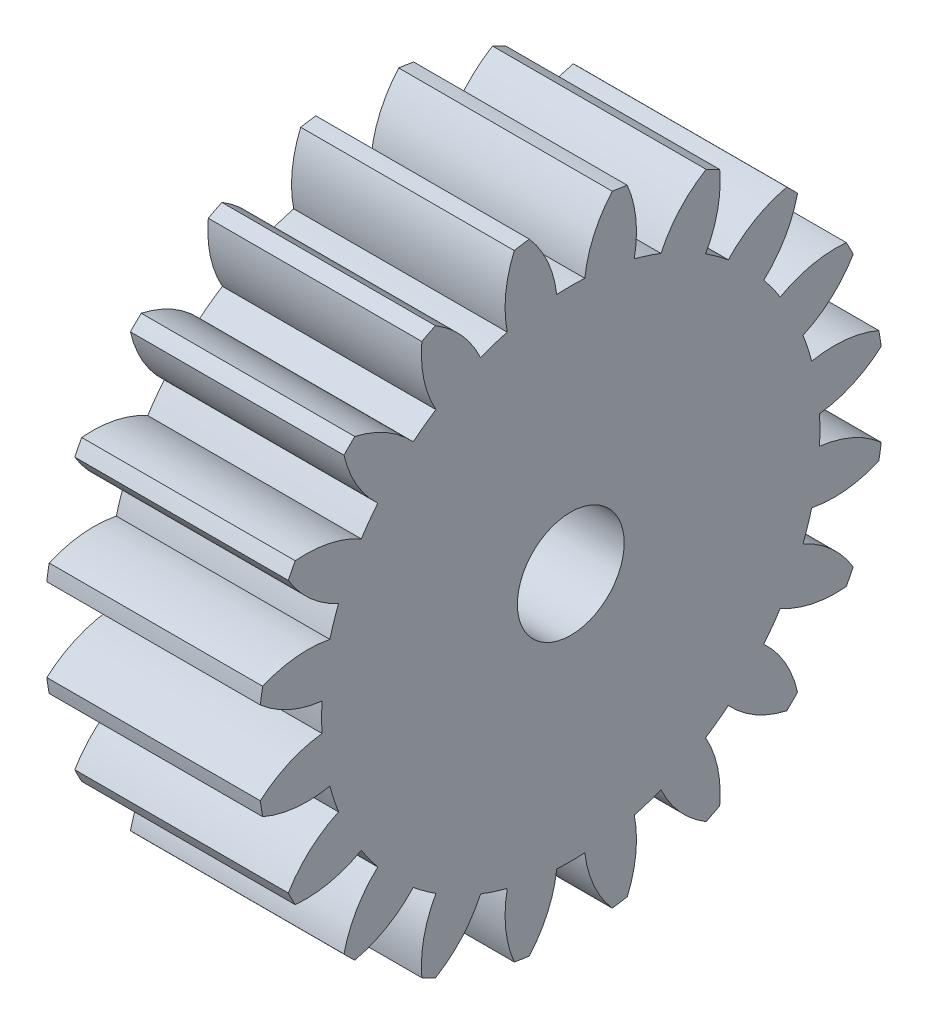
SolidWorks part; units mm, degrees
material "Ottone"
ref_plane "Plane1" through (0, 0, 0) normal (0, 0, 1) x (1, 0, 0)
ref_plane "Plane2" through (0, 0, 0) normal (0, 1, 0) x (1, 0, 0)
ref_plane "Plane3" through (0, 0, 0) normal (1, 0, 0) x (0, 0, -1)
sketch "HoldingSke" plane through (0, 0, 0) normal (0, 1, 0) x (1, 0, 0)
  line L0 (0, 0) -> (0.1879, -0.0684)
  line L1 (-15, 0) -> (100, 0) construction
  line L2 (0, 0) -> (-2.1039, 2.3779)
  line L3 (0, 0) -> (-11.863, 4.5341)
  line L4 (0, 0) -> (8.1152, 2.9537)
  line L5 (0, 0) -> (-46.8476, -17.4728)
  line L6 (0, 0) -> (-16.5793, -11.1861)
  line L7 (-2.1039, 2.3779) -> (8.6586, 51.2059)
  line L8 (-76.2, 54.61) -> (-73.9, 54.61)
  line L9 (-71.009, 38.7566) -> (-53.1078, 45.2721)
  line L10 (-76.2, 71.12) -> (104.1128, 71.12)
  line L11 (0, 0) -> (-20, 0)
  line L12 (-76.2, 101.6) -> (-76.033, 101.6)
  line L13 (24.9733, 27.94) -> (52.9518, 28.4284)
  line L14 (24.9733, 27.94) -> (24.9743, 27.94)
  line L15 (24.9733, 27.94) -> (100.4006, 29.5858)
  line L16 (-63.627, -5) -> (-12.827, -5)
  circle A0 centre (0, 0) radius 7.5
  circle A1 centre (0, 0) radius 37.5
  circle A2 centre (0, 0) radius 37.5
  circle A3 centre (0, 0) radius 7.5
  dimension "MHD" = 75
  dimension "Hub_dia" = 75
  dimension "Bore" = 15
  dimension "MBD" = 15
  dimension "Num_teeth" = 20
  dimension "Pitch" = 0.2
  dimension "Overall_len" = 50
  dimension "Show_teeth" = 20
  dimension "Thickness" = 20
  dimension "OAL" = 50.0001
  dimension "T_dim" = 2.3
  dimension "Ap" = 20
  dimension "H" = 19.05
  dimension "Pitch_radius" = 180.3128
  dimension "Width" = 20
  dimension "Backlash" = 0.167
  dimension "Addendum_fac" = 1
  dimension "Dedendum_fac" = 1.25
  dimension "Clearance_fac" = 0.25
  dimension "Dedendum_add" = 0.001
  dimension "Module" = 5
sketch "BasProSke" plane through (0, 0, 0) normal (0, 1, 0) x (1, 0, 0)
  line L0 (-10, 0) -> (60, 0) construction
  line L1 (0, 0) -> (0, 55)
  line L2 (0, 0) -> (20, 0)
  line L3 (20, 0) -> (20, 55)
  line L4 (20, 55) -> (0, 55)
  dimension "Thickness" = 20
  dimension "Diameter" = 110
revolve "Base-Revolve" add sketch "BasProSke" angle 360 about L0
sketch "TooCutSke" plane through (0, 0, 0) normal (1, 0, 0) x (0, 0, -1)
  line L1 (0, 0) -> (0, 107) construction
  line L2 (0, 0) -> (-4.2151, 49.822) construction
  line L3 (0, 0) -> (-15.6021, 98.5081) construction
  line L4 (-4.2151, 49.822) -> (-7.8011, 49.254) construction
  arc A0 (2.4648, 43.6795) -> (-2.4648, 43.6795) centre (0, 0) ccw
  arc A1 (7.3009, 54.5389) -> (-7.3009, 54.5389) centre (0, 0) ccw
  circle A2 centre (0, 0) radius 50 construction
  circle A3 centre (0, 0) radius 46.9846 construction
  arc A4 (-2.4648, 43.6795) -> (-7.3009, 54.5389) centre (-22.3276, 41.3405) ccw
  arc A5 (7.3009, 54.5389) -> (2.4648, 43.6795) centre (22.3276, 41.3405) ccw
  dimension "Root_dia" = 87.498
  dimension "Overcut_dia" = 110.0508
  dimension "Pitch_dia" = 100
  dimension "Base_dia" = 93.9693
  dimension "Flank_rad" = 20
  dimension "Half_ang" = 9
  dimension "Half_CT" = 3.6307
extrude "ToothCut" cut sketch "TooCutSke" along normal through all
fillet "Breaks" [suppressed] radius 0.1 tangent propagation no
fillet "RootFillets" [suppressed] radius 1.251
pattern_circular "TeethCuts" count 20 every 18 about axis through (-10, 0, 0) along (1, 0, 0) of "ToothCut"
sketch "HubNeaOneSke" [suppressed] plane through (0, 0, 0) normal (-1, 0, 0) x (0, 0, 1)
  circle A0 centre (0, 0) radius 12.7
  dimension "Diameter" = 75
extrude "HubNearOne" [suppressed] add sketch "HubNeaOneSke" along normal blind 30.0001
sketch "HubNeaBotSke" [suppressed] plane through (0, 0, 0) normal (-1, 0, 0) x (0, 0, 1)
  circle A0 centre (0, 0) radius 12.7
  dimension "Diameter" = 75
extrude "HubNearBoth" [suppressed] add sketch "HubNeaBotSke" along normal blind 15
ref_plane "FarPln" through (20, 0, 0) normal (1, 0, 0) x (0, 0, -1)
sketch "HubFarSke" [suppressed] plane through (12.7, 0, 0) normal (1, 0, 0) x (0, 0, -1)
  circle A0 centre (0, 0) radius 12.7
  dimension "Diameter" = 75
extrude "HubFar" [suppressed] add sketch "HubFarSke" along normal blind 15
sketch "BorSke" plane through (0, 0, 0) normal (1, 0, 0) x (0, 0, -1)
  circle A0 centre (0, 0) radius 7.5
  dimension "Diameter" = 15
extrude "Bore" cut sketch "BorSke" along normal mid plane 100.0001
sketch "KeySke" [suppressed] plane through (0, 0, 0) normal (1, 0, 0) x (0, 0, -1)
  line L0 (-3.175, 0) -> (-3.175, 12.065)
  line L1 (-3.175, 12.065) -> (3.175, 12.065)
  line L2 (3.175, 12.065) -> (3.175, 0)
  line L3 (0, 0) -> (0, 34) construction
  line L4 (-3.175, 0) -> (3.175, 0)
  dimension "Offset" = 9.8
  dimension "Width" = 5
extrude "Keyway" [suppressed] cut sketch "KeySke" along normal mid plane 100.0001
pattern_circular "Keyway2" [suppressed] count 2 every 90 about axis through (-10, 0, 0) along (1, 0, 0) reverse direction yes
ref_axis "Axis1" through (20, 0, 0) along (-1, 0, 0)
scale "Scala1" scale about centroid uniform scaling yes scale factor 0.16
sketch "Schizzo1" plane through (11.6, 0, 0) normal (1, 0, 0) x (0, 0, -1)
  arc A80 (-8.7226, 1.1649) -> (-6.9887, 0.3944) centre (-6.6145, 3.5724) ccw
  arc A81 (-6.9887, 0.3944) -> (-6.9887, -0.3944) centre (0, 0) ccw
  arc A82 (-6.9887, -0.3944) -> (-8.7226, -1.1649) centre (-6.6145, -3.5724) ccw
  arc A83 (-8.7226, -1.1649) -> (-8.6556, -1.5875) centre (0, 0) ccw
  arc A84 (-8.6556, -1.5875) -> (-6.7685, -1.7846) centre (-7.3947, 1.3536) ccw
  arc A85 (-6.7685, -1.7846) -> (-6.5248, -2.5347) centre (0, 0) ccw
  arc A86 (-6.5248, -2.5347) -> (-7.9357, -3.8033) centre (-5.1868, -5.4416) ccw
  arc A87 (-7.9357, -3.8033) -> (-7.7414, -4.1845) centre (0, 0) ccw
  arc A88 (-7.7414, -4.1845) -> (-5.8858, -3.7888) centre (-7.451, -0.9977) ccw
  arc A89 (-5.8858, -3.7888) -> (-5.4222, -4.4269) centre (0, 0) ccw
  arc A90 (-5.4222, -4.4269) -> (-6.372, -6.0694) centre (-3.2514, -6.778) ccw
  arc A91 (-6.372, -6.0694) -> (-6.0694, -6.372) centre (0, 0) ccw
  arc A92 (-6.0694, -6.372) -> (-4.4269, -5.4222) centre (-6.778, -3.2514) ccw
  arc A93 (-4.4269, -5.4222) -> (-3.7888, -5.8858) centre (0, 0) ccw
  arc A94 (-3.7888, -5.8858) -> (-4.1845, -7.7414) centre (-0.9977, -7.451) ccw
  arc A95 (-4.1845, -7.7414) -> (-3.8033, -7.9357) centre (0, 0) ccw
  arc A96 (-3.8033, -7.9357) -> (-2.5347, -6.5248) centre (-5.4416, -5.1868) ccw
  arc A97 (-2.5347, -6.5248) -> (-1.7846, -6.7685) centre (0, 0) ccw
  arc A98 (-1.7846, -6.7685) -> (-1.5875, -8.6556) centre (1.3536, -7.3947) ccw
  arc A99 (-1.5875, -8.6556) -> (-1.1649, -8.7226) centre (0, 0) ccw
  arc A100 (-1.1649, -8.7226) -> (-0.3944, -6.9887) centre (-3.5724, -6.6145) ccw
  arc A101 (-0.3944, -6.9887) -> (0.3944, -6.9887) centre (0, 0) ccw
  arc A102 (0.3944, -6.9887) -> (1.1649, -8.7226) centre (3.5724, -6.6145) ccw
  arc A103 (1.1649, -8.7226) -> (1.5875, -8.6556) centre (0, 0) ccw
  arc A104 (1.5875, -8.6556) -> (1.7846, -6.7685) centre (-1.3536, -7.3947) ccw
  arc A105 (1.7846, -6.7685) -> (2.5347, -6.5248) centre (0, 0) ccw
  arc A106 (2.5347, -6.5248) -> (3.8033, -7.9357) centre (5.4416, -5.1868) ccw
  arc A107 (3.8033, -7.9357) -> (4.1845, -7.7414) centre (0, 0) ccw
  arc A108 (4.1845, -7.7414) -> (3.7888, -5.8858) centre (0.9977, -7.451) ccw
  arc A109 (3.7888, -5.8858) -> (4.4269, -5.4222) centre (0, 0) ccw
  arc A110 (4.4269, -5.4222) -> (6.0694, -6.372) centre (6.778, -3.2514) ccw
  arc A111 (6.0694, -6.372) -> (6.372, -6.0694) centre (0, 0) ccw
  arc A112 (6.372, -6.0694) -> (5.4222, -4.4269) centre (3.2514, -6.778) ccw
  arc A113 (5.4222, -4.4269) -> (5.8858, -3.7888) centre (0, 0) ccw
  arc A114 (5.8858, -3.7888) -> (7.7414, -4.1845) centre (7.451, -0.9977) ccw
  arc A115 (7.7414, -4.1845) -> (7.9357, -3.8033) centre (0, 0) ccw
  arc A116 (7.9357, -3.8033) -> (6.5248, -2.5347) centre (5.1868, -5.4416) ccw
  arc A117 (6.5248, -2.5347) -> (6.7685, -1.7846) centre (0, 0) ccw
  arc A118 (6.7685, -1.7846) -> (8.6556, -1.5875) centre (7.3947, 1.3536) ccw
  arc A119 (8.6556, -1.5875) -> (8.7226, -1.1649) centre (0, 0) ccw
  arc A120 (8.7226, -1.1649) -> (6.9887, -0.3944) centre (6.6145, -3.5724) ccw
  arc A121 (6.9887, -0.3944) -> (6.9887, 0.3944) centre (0, 0) ccw
  arc A122 (6.9887, 0.3944) -> (8.7226, 1.1649) centre (6.6145, 3.5724) ccw
  arc A123 (8.7226, 1.1649) -> (8.6556, 1.5875) centre (0, 0) ccw
  arc A124 (8.6556, 1.5875) -> (6.7685, 1.7846) centre (7.3947, -1.3536) ccw
  arc A125 (6.7685, 1.7846) -> (6.5248, 2.5347) centre (0, 0) ccw
  arc A126 (6.5248, 2.5347) -> (7.9357, 3.8033) centre (5.1868, 5.4416) ccw
  arc A127 (7.9357, 3.8033) -> (7.7414, 4.1845) centre (0, 0) ccw
  arc A128 (7.7414, 4.1845) -> (5.8858, 3.7888) centre (7.451, 0.9977) ccw
  arc A129 (5.8858, 3.7888) -> (5.4222, 4.4269) centre (0, 0) ccw
  arc A130 (5.4222, 4.4269) -> (6.372, 6.0694) centre (3.2514, 6.778) ccw
  arc A131 (6.372, 6.0694) -> (6.0694, 6.372) centre (0, 0) ccw
  arc A132 (6.0694, 6.372) -> (4.4269, 5.4222) centre (6.778, 3.2514) ccw
  arc A133 (4.4269, 5.4222) -> (3.7888, 5.8858) centre (0, 0) ccw
  arc A134 (3.7888, 5.8858) -> (4.1845, 7.7414) centre (0.9977, 7.451) ccw
  arc A135 (4.1845, 7.7414) -> (3.8033, 7.9357) centre (0, 0) ccw
  arc A136 (3.8033, 7.9357) -> (2.5347, 6.5248) centre (5.4416, 5.1868) ccw
  arc A137 (2.5347, 6.5248) -> (1.7846, 6.7685) centre (0, 0) ccw
  arc A138 (1.7846, 6.7685) -> (1.5875, 8.6556) centre (-1.3536, 7.3947) ccw
  arc A139 (1.5875, 8.6556) -> (1.1649, 8.7226) centre (0, 0) ccw
  arc A140 (1.1649, 8.7226) -> (0.3944, 6.9887) centre (3.5724, 6.6145) ccw
  arc A141 (0.3944, 6.9887) -> (-0.3944, 6.9887) centre (0, 0) ccw
  arc A142 (-0.3944, 6.9887) -> (-1.1649, 8.7226) centre (-3.5724, 6.6145) ccw
  arc A143 (-1.1649, 8.7226) -> (-1.5875, 8.6556) centre (0, 0) ccw
  arc A144 (-1.5875, 8.6556) -> (-1.7846, 6.7685) centre (1.3536, 7.3947) ccw
  arc A145 (-1.7846, 6.7685) -> (-2.5347, 6.5248) centre (0, 0) ccw
  arc A146 (-2.5347, 6.5248) -> (-3.8033, 7.9357) centre (-5.4416, 5.1868) ccw
  arc A147 (-3.8033, 7.9357) -> (-4.1845, 7.7414) centre (0, 0) ccw
  arc A148 (-4.1845, 7.7414) -> (-3.7888, 5.8858) centre (-0.9977, 7.451) ccw
  arc A149 (-3.7888, 5.8858) -> (-4.4269, 5.4222) centre (0, 0) ccw
  arc A150 (-4.4269, 5.4222) -> (-6.0694, 6.372) centre (-6.778, 3.2514) ccw
  arc A151 (-6.0694, 6.372) -> (-6.372, 6.0694) centre (0, 0) ccw
  arc A152 (-6.372, 6.0694) -> (-5.4222, 4.4269) centre (-3.2514, 6.778) ccw
  arc A153 (-5.4222, 4.4269) -> (-5.8858, 3.7888) centre (0, 0) ccw
  arc A154 (-5.8858, 3.7888) -> (-7.7414, 4.1845) centre (-7.451, 0.9977) ccw
  arc A155 (-7.7414, 4.1845) -> (-7.9357, 3.8033) centre (0, 0) ccw
  arc A156 (-7.9357, 3.8033) -> (-6.5248, 2.5347) centre (-5.1868, 5.4416) ccw
  arc A157 (-6.5248, 2.5347) -> (-6.7685, 1.7846) centre (0, 0) ccw
  arc A158 (-6.7685, 1.7846) -> (-8.6556, 1.5875) centre (-7.3947, -1.3536) ccw
  arc A159 (-8.6556, 1.5875) -> (-8.7226, 1.1649) centre (0, 0) ccw
  arc A160 (-8.7226, 1.1649) -> (-6.9887, 0.3944) centre (-6.6145, 3.5724) ccw
  arc A161 (-6.9887, 0.3944) -> (-6.9887, -0.3944) centre (0, 0) ccw
  arc A162 (-6.9887, -0.3944) -> (-8.7226, -1.1649) centre (-6.6145, -3.5724) ccw
  arc A163 (-8.7226, -1.1649) -> (-8.6556, -1.5875) centre (0, 0) ccw
  arc A164 (-8.6556, -1.5875) -> (-6.7685, -1.7846) centre (-7.3947, 1.3536) ccw
  arc A165 (-6.7685, -1.7846) -> (-6.5248, -2.5347) centre (0, 0) ccw
  arc A166 (-6.5248, -2.5347) -> (-7.9357, -3.8033) centre (-5.1868, -5.4416) ccw
  arc A167 (-7.9357, -3.8033) -> (-7.7414, -4.1845) centre (0, 0) ccw
  arc A168 (-7.7414, -4.1845) -> (-5.8858, -3.7888) centre (-7.451, -0.9977) ccw
  arc A169 (-5.8858, -3.7888) -> (-5.4222, -4.4269) centre (0, 0) ccw
  arc A170 (-5.4222, -4.4269) -> (-6.372, -6.0694) centre (-3.2514, -6.778) ccw
  arc A171 (-6.372, -6.0694) -> (-6.0694, -6.372) centre (0, 0) ccw
  arc A172 (-6.0694, -6.372) -> (-4.4269, -5.4222) centre (-6.778, -3.2514) ccw
  arc A173 (-4.4269, -5.4222) -> (-3.7888, -5.8858) centre (0, 0) ccw
  arc A174 (-3.7888, -5.8858) -> (-4.1845, -7.7414) centre (-0.9977, -7.451) ccw
  arc A175 (-4.1845, -7.7414) -> (-3.8033, -7.9357) centre (0, 0) ccw
  arc A176 (-3.8033, -7.9357) -> (-2.5347, -6.5248) centre (-5.4416, -5.1868) ccw
  arc A177 (-2.5347, -6.5248) -> (-1.7846, -6.7685) centre (0, 0) ccw
  arc A178 (-1.7846, -6.7685) -> (-1.5875, -8.6556) centre (1.3536, -7.3947) ccw
  arc A179 (-1.5875, -8.6556) -> (-1.1649, -8.7226) centre (0, 0) ccw
  arc A180 (-1.1649, -8.7226) -> (-0.3944, -6.9887) centre (-3.5724, -6.6145) ccw
  arc A181 (-0.3944, -6.9887) -> (0.3944, -6.9887) centre (0, 0) ccw
  arc A182 (0.3944, -6.9887) -> (1.1649, -8.7226) centre (3.5724, -6.6145) ccw
  arc A183 (1.1649, -8.7226) -> (1.5875, -8.6556) centre (0, 0) ccw
  arc A184 (1.5875, -8.6556) -> (1.7846, -6.7685) centre (-1.3536, -7.3947) ccw
  arc A185 (1.7846, -6.7685) -> (2.5347, -6.5248) centre (0, 0) ccw
  arc A186 (2.5347, -6.5248) -> (3.8033, -7.9357) centre (5.4416, -5.1868) ccw
  arc A187 (3.8033, -7.9357) -> (4.1845, -7.7414) centre (0, 0) ccw
  arc A188 (4.1845, -7.7414) -> (3.7888, -5.8858) centre (0.9977, -7.451) ccw
  arc A189 (3.7888, -5.8858) -> (4.4269, -5.4222) centre (0, 0) ccw
  arc A190 (4.4269, -5.4222) -> (6.0694, -6.372) centre (6.778, -3.2514) ccw
  arc A191 (6.0694, -6.372) -> (6.372, -6.0694) centre (0, 0) ccw
  arc A192 (6.372, -6.0694) -> (5.4222, -4.4269) centre (3.2514, -6.778) ccw
  arc A193 (5.4222, -4.4269) -> (5.8858, -3.7888) centre (0, 0) ccw
  arc A194 (5.8858, -3.7888) -> (7.7414, -4.1845) centre (7.451, -0.9977) ccw
  arc A195 (7.7414, -4.1845) -> (7.9357, -3.8033) centre (0, 0) ccw
  arc A196 (7.9357, -3.8033) -> (6.5248, -2.5347) centre (5.1868, -5.4416) ccw
  arc A197 (6.5248, -2.5347) -> (6.7685, -1.7846) centre (0, 0) ccw
  arc A198 (6.7685, -1.7846) -> (8.6556, -1.5875) centre (7.3947, 1.3536) ccw
  arc A199 (8.6556, -1.5875) -> (8.7226, -1.1649) centre (0, 0) ccw
  arc A200 (8.7226, -1.1649) -> (6.9887, -0.3944) centre (6.6145, -3.5724) ccw
  arc A201 (6.9887, -0.3944) -> (6.9887, 0.3944) centre (0, 0) ccw
  arc A202 (6.9887, 0.3944) -> (8.7226, 1.1649) centre (6.6145, 3.5724) ccw
  arc A203 (8.7226, 1.1649) -> (8.6556, 1.5875) centre (0, 0) ccw
  arc A204 (8.6556, 1.5875) -> (6.7685, 1.7846) centre (7.3947, -1.3536) ccw
  arc A205 (6.7685, 1.7846) -> (6.5248, 2.5347) centre (0, 0) ccw
  arc A206 (6.5248, 2.5347) -> (7.9357, 3.8033) centre (5.1868, 5.4416) ccw
  arc A207 (7.9357, 3.8033) -> (7.7414, 4.1845) centre (0, 0) ccw
  arc A208 (7.7414, 4.1845) -> (5.8858, 3.7888) centre (7.451, 0.9977) ccw
  arc A209 (5.8858, 3.7888) -> (5.4222, 4.4269) centre (0, 0) ccw
  arc A210 (5.4222, 4.4269) -> (6.372, 6.0694) centre (3.2514, 6.778) ccw
  arc A211 (6.372, 6.0694) -> (6.0694, 6.372) centre (0, 0) ccw
  arc A212 (6.0694, 6.372) -> (4.4269, 5.4222) centre (6.778, 3.2514) ccw
  arc A213 (4.4269, 5.4222) -> (3.7888, 5.8858) centre (0, 0) ccw
  arc A214 (3.7888, 5.8858) -> (4.1845, 7.7414) centre (0.9977, 7.451) ccw
  arc A215 (4.1845, 7.7414) -> (3.8033, 7.9357) centre (0, 0) ccw
  arc A216 (3.8033, 7.9357) -> (2.5347, 6.5248) centre (5.4416, 5.1868) ccw
  arc A217 (2.5347, 6.5248) -> (1.7846, 6.7685) centre (0, 0) ccw
  arc A218 (1.7846, 6.7685) -> (1.5875, 8.6556) centre (-1.3536, 7.3947) ccw
  arc A219 (1.5875, 8.6556) -> (1.1649, 8.7226) centre (0, 0) ccw
  arc A220 (1.1649, 8.7226) -> (0.3944, 6.9887) centre (3.5724, 6.6145) ccw
  arc A221 (0.3944, 6.9887) -> (-0.3944, 6.9887) centre (0, 0) ccw
  arc A222 (-0.3944, 6.9887) -> (-1.1649, 8.7226) centre (-3.5724, 6.6145) ccw
  arc A223 (-1.1649, 8.7226) -> (-1.5875, 8.6556) centre (0, 0) ccw
  arc A224 (-1.5875, 8.6556) -> (-1.7846, 6.7685) centre (1.3536, 7.3947) ccw
  arc A225 (-1.7846, 6.7685) -> (-2.5347, 6.5248) centre (0, 0) ccw
  arc A226 (-2.5347, 6.5248) -> (-3.8033, 7.9357) centre (-5.4416, 5.1868) ccw
  arc A227 (-3.8033, 7.9357) -> (-4.1845, 7.7414) centre (0, 0) ccw
  arc A228 (-4.1845, 7.7414) -> (-3.7888, 5.8858) centre (-0.9977, 7.451) ccw
  arc A229 (-3.7888, 5.8858) -> (-4.4269, 5.4222) centre (0, 0) ccw
  arc A230 (-4.4269, 5.4222) -> (-6.0694, 6.372) centre (-6.778, 3.2514) ccw
  arc A231 (-6.0694, 6.372) -> (-6.372, 6.0694) centre (0, 0) ccw
  arc A232 (-6.372, 6.0694) -> (-5.4222, 4.4269) centre (-3.2514, 6.778) ccw
  arc A233 (-5.4222, 4.4269) -> (-5.8858, 3.7888) centre (0, 0) ccw
  arc A234 (-5.8858, 3.7888) -> (-7.7414, 4.1845) centre (-7.451, 0.9977) ccw
  arc A235 (-7.7414, 4.1845) -> (-7.9357, 3.8033) centre (0, 0) ccw
  arc A236 (-7.9357, 3.8033) -> (-6.5248, 2.5347) centre (-5.1868, 5.4416) ccw
  arc A237 (-6.5248, 2.5347) -> (-6.7685, 1.7846) centre (0, 0) ccw
  arc A238 (-6.7685, 1.7846) -> (-8.6556, 1.5875) centre (-7.3947, -1.3536) ccw
  arc A239 (-8.6556, 1.5875) -> (-8.7226, 1.1649) centre (0, 0) ccw
  dimension "D1" = 0
extrude "Estrusione-Estrusione1" add sketch "Schizzo1" along normal blind 2.8
sketch "Schizzo2" plane through (8.4, 0, 0) normal (-1, 0, 0) x (0, 0, 1)
  circle A0 centre (0, 0) radius 2.85
  dimension "D1" = 5.7
extrude "Taglio-Estrusione1" cut sketch "Schizzo2" against normal blind 3.3
sketch "Schizzo3" plane through (11.7, 0, 0) normal (-1, 0, 0) x (0, 0, 1)
  circle A0 centre (0, 0) radius 1.5
extrude "Taglio-Estrusione2" cut sketch "Schizzo3" against normal blind 3.3
equation "' \"Module@HoldingSke\" = 6.35"
equation "' \"Num_teeth@HoldingSke\" = 12"
equation "' \"Ap@HoldingSke\" =  20"
equation "' \"Ap@HoldingSke\" = 20"
equation "' \"Width@HoldingSke\" = 0.5 * 25.4"
equation "' \"Hub_dia@HoldingSke\"= 1 * 25.4"
equation "' \"Hub_dia@HoldingSke\" = 1 * 25.4"
equation "' \"Overall_len@HoldingSke\" = 1.0 * 25.4"
equation "' \"Bore@HoldingSke\" = 0.75 * 25.4"
equation "' \"T_dim@HoldingSke\" = 0.1 * 25.4"
equation "' \"Width@KeySke\" = 0.25 * 25.4"
equation "' \"Show_teeth@HoldingSke\" = 13"
equation "' \"Backlash@HoldingSke\" = 0.009 * 25.4"
equation "' \"Addendum_fac@HoldingSke\" = 1.0"
equation "' \"Dedendum_fac@HoldingSke\" = 1.25"
equation "' \"Dedendum_add@HoldingSke\" = 0.00005 * 25.4"
equation "' \"Clearance_fac@HoldingSke\" = 0.25"
equation "\"Pitch@HoldingSke\" = 1 / \"Module@HoldingSke\""
equation "\"Overcut_dia@TooCutSke\" = (\"Num_teeth@HoldingSke\" + 2 * \"Addendum_fac@HoldingSke\") / \"Pitch@HoldingSke\" + 0.002 * 25.4"
equation "\"Pitch_dia@TooCutSke\" = \"Num_teeth@HoldingSke\" / \"Pitch@HoldingSke\""
equation "\"Base_dia@TooCutSke\" = \"Num_teeth@HoldingSke\" / \"Pitch@HoldingSke\" * cos((\"Ap@HoldingSke\"  * 3.14159265 / 180))"
equation "\"Root_dia@TooCutSke\" = (\"Num_teeth@HoldingSke\" + 2) / \"Pitch@HoldingSke\" - 2 * (\"Addendum_fac@HoldingSke\" + \"Dedendum_fac@HoldingSke\") / \"Pitch@HoldingSke\" - \"Dedendum_add@HoldingSke\" * 2"
equation "\"Half_ang@TooCutSke\" = 180 / \"Num_teeth@HoldingSke\""
equation "\"Half_CT@TooCutSke\" = \"Num_teeth@HoldingSke\" / \"Pitch@HoldingSke\" * sin((3.14159265 / 2 / \"Num_teeth@HoldingSke\")) / 2 - 7 * \"Backlash@HoldingSke\" / 4"
equation "\"Flank_rad@TooCutSke\" = \"Num_teeth@HoldingSke\" / \"Pitch@HoldingSke\" / 5"
equation "\"Radius@RootFillets\" = \"Clearance_fac@HoldingSke\" / \"Pitch@HoldingSke\" + \"Dedendum_add@HoldingSke\""
equation "\"Break_rad@Breaks\" = 0.02 / \"Pitch@HoldingSke\""
equation "\"Thickness@HoldingSke\" = \"Width@HoldingSke\""
equation "\"OAL@HoldingSke\" = \"Thickness@HoldingSke\""
equation "\"MHD@HoldingSke\" = (\"Num_teeth@HoldingSke\" + 2) / \"Pitch@HoldingSke\" - 2 * (\"Addendum_fac@HoldingSke\" + \"Dedendum_fac@HoldingSke\")  / \"Pitch@HoldingSke\" - \"Dedendum_add@HoldingSke\" * 2"
equation "\"MBD@HoldingSke\" = (\"Num_teeth@HoldingSke\" + 2) / \"Pitch@HoldingSke\" - 2 * (\"Addendum_fac@HoldingSke\" + \"Dedendum_fac@HoldingSke\")  / \"Pitch@HoldingSke\" - \"Dedendum_add@HoldingSke\" * 2 - 0.002 * 25.4"
equation "\"MHD@HoldingSke\" = ((sgn( \"MHD@HoldingSke\" - \"Hub_dia@HoldingSke\" )-1)*( \"MHD@HoldingSke\" - \"Hub_dia@HoldingSke\" ))/-2+ \"Hub_dia@HoldingSke\""
equation "\"MBD@HoldingSke\" = ((sgn( \"MBD@HoldingSke\" - \"Bore@HoldingSke\" )-1)*( \"MBD@HoldingSke\" - \"Bore@HoldingSke\" ))/-2+ \"Bore@HoldingSke\""
equation "\"OAL@HoldingSke\" = ((sgn( \"OAL@HoldingSke\" - \"Overall_len@HoldingSke\" )+1)*( \"OAL@HoldingSke\" - \"Overall_len@HoldingSke\" ))/2 + \"Overall_len@HoldingSke\" + 0.000002 * 25.4"
equation "\"Num_teeth@TeethCuts\"=int( \"Show_teeth@HoldingSke\" ) "
equation "\"Num_teeth@TeethCuts\" = ((sgn( \"Num_teeth@TeethCuts\" - \"Num_teeth@HoldingSke\" )-1)*( \"Num_teeth@TeethCuts\" - \"Num_teeth@HoldingSke\" ))/-2+ \"Num_teeth@HoldingSke\""
equation "\"Angle@TeethCuts\" = 360.0 / \"Num_teeth@HoldingSke\""
equation "\"Diameter@BasProSke\" = (\"Num_teeth@HoldingSke\" + 2 * \"Addendum_fac@HoldingSke\") / \"Pitch@HoldingSke\""
equation "\"Thickness@BasProSke\"  = \"Thickness@HoldingSke\""
equation "' \"Fillet_rad@BasProSke\" =  \"Thickness@HoldingSke\" * 0.05"
equation "' \"Fillet_rad@BasProSke\" = \"Thickness@HoldingSke\" * 0.05"
equation "\"MHD@HoldingSke\" = ((sgn( \"MHD@HoldingSke\" - \"Root_dia@TooCutSke\" )-1)*( \"MHD@HoldingSke\" - \"Root_dia@TooCutSke\" ))/-2+ \"Root_dia@TooCutSke\""
equation "\"Diameter@HubNeaOneSke\" = \"MHD@HoldingSke\""
equation "\"Length@HubNearOne\" = \"OAL@HoldingSke\" - \"Thickness@BasProSke\""
equation "\"Diameter@HubNeaBotSke\" = \"MHD@HoldingSke\""
equation "\"Length@HubNearBoth\" = ( \"OAL@HoldingSke\" - \"Thickness@BasProSke\" ) / 2.0"
equation "\"Thickness@FarPln\" = \"Thickness@BasProSke\""
equation "\"Diameter@HubFarSke\" = \"MHD@HoldingSke\""
equation "\"Length@HubFar\" = ( \"OAL@HoldingSke\" - \"Thickness@BasProSke\" ) / 2.0"
equation "\"Diameter@BorSke\" = \"MBD@HoldingSke\""
equation "\"D1@Bore\" = \"OAL@HoldingSke\" * 2.0"
equation "\"D1@Keyway\" = \"OAL@HoldingSke\" * 2.0"
equation "\"Offset@KeySke\" = \"T_dim@HoldingSke\" + \"MBD@HoldingSke\" / 2.0"
